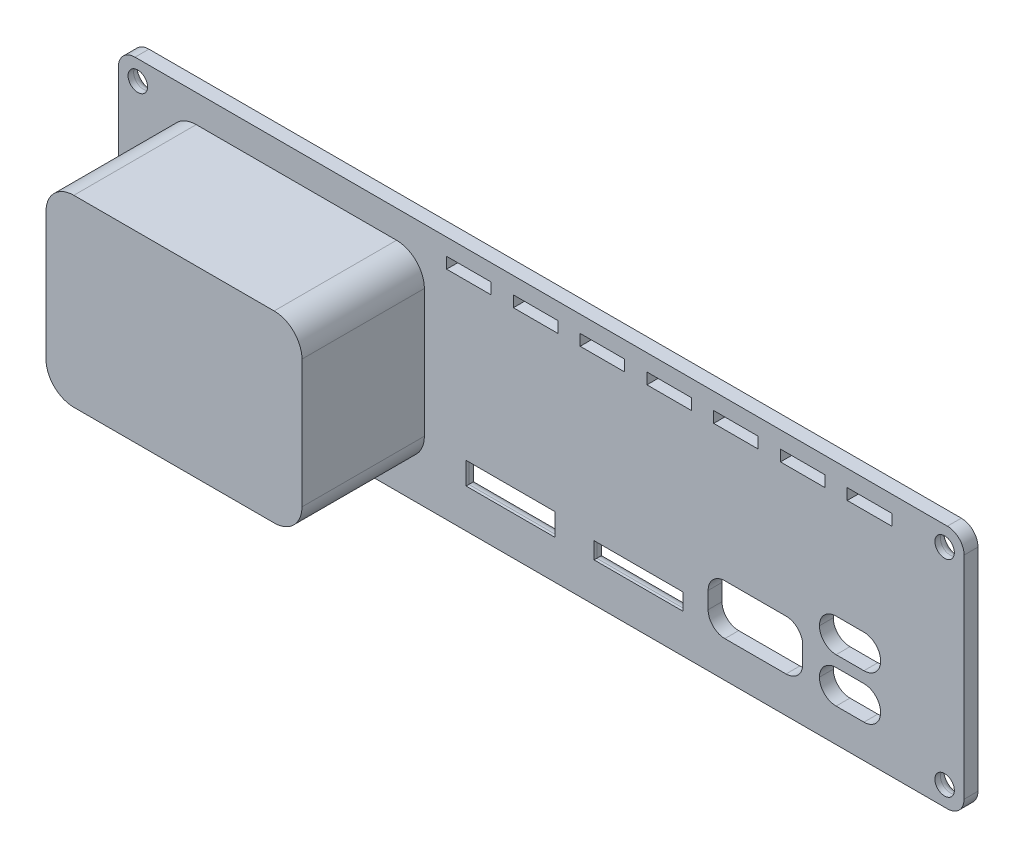
SolidWorks part; units mm, degrees
ref_plane "Front Plane" through (0, 0, 0) normal (0, 0, 1) x (1, 0, 0)
ref_plane "Top Plane" through (0, 0, 0) normal (0, 1, 0) x (1, 0, 0)
ref_plane "Right Plane" through (0, 0, 0) normal (1, 0, 0) x (0, 0, -1)
sketch "Sketch1" plane through (0, 0, 0) normal (0, 0, 1) x (1, 0, 0)
  line L1 (76, -22) -> (-76, -22)
  line L2 (76, -22) -> (76, 22)
  line L3 (76, 22) -> (-76, 22)
  line L4 (-76, -22) -> (-76, 22)
  line L5 (76, -22) -> (-76, 22) construction
  line L6 (76, 22) -> (-76, -22) construction
  point P0 (0, 0)
  dimension "D1" = 152
  dimension "D2" = 44
extrude "main_body" add sketch "Sketch1" along normal blind 2.5
fillet "body_corners" radius 3 4 edges at (-76, -22, 1.25) (76, -22, 1.25) (76, 22, 1.25) (-76, 22, 1.25)
sketch "Sketch2" plane through (0, 0, 2.5) normal (0, 0, 1) x (1, 0, 0)
  line L0 (-76, 18.5) -> (76, 18.5) construction
  line L1 (-76, 19) -> (-76, -19) construction
  line L2 (76, -19) -> (76, 19) construction
  line L3 (-72.5, 22) -> (-72.5, -22) construction
  line L4 (-76, -18.5) -> (76, -18.5) construction
  line L8 (73, 22) -> (-73, 22) construction
  line L9 (72.5, 22) -> (72.5, -22) construction
  line L10 (-73, -22) -> (73, -22) construction
  circle A1 centre (-72.5, -18.5) radius 1.75
  circle A2 centre (72.5, 18.5) radius 1.75
  circle A3 centre (72.5, -18.5) radius 1.75
  circle A4 centre (-72.5, 18.5) radius 1.75
  dimension "D5" = 3.5
  dimension "D6" = 3.5
  dimension "D7" = 3.5
  dimension "D8" = 3.5
  dimension "D1" = 3.5
  dimension "D2" = 3.5
  dimension "D3" = 3.5
  dimension "D4" = 3.5
extrude "mounting_holes" cut sketch "Sketch2" against normal through all
fillet "bolt_heads" radius 1.5 4 edges at (-70.75, -18.5, 0) (-70.75, 18.5, 0) (74.25, -18.5, 0) (74.25, 18.5, 0)
sketch "Sketch3" plane through (0, 0, 2.5) normal (0, 0, 1) x (1, 0, 0)
  line L0 (-76, 5) -> (76, 5) construction
  line L1 (-76, 19) -> (-76, -19) construction
  line L2 (76, -19) -> (76, 19) construction
  line L3 (73, 22) -> (-73, 22) construction
  line L4 (-73, -22) -> (73, -22) construction
  line L5 (0, 22) -> (0, -22) construction
  line L6 (76, -19) -> (76, 19) construction
  line L8 (50, -2) -> (61, -2)
  line L10 (50, -2) -> (50, -8)
  line L11 (50, -8) -> (61, -8)
  line L13 (61, -2) -> (61, -8)
  line L14 (50, -2) -> (61, -8) construction
  line L16 (50, -8) -> (61, -2) construction
  line L17 (30, -6.5) -> (47, -6.5)
  line L18 (30, -6.5) -> (30, -15.5)
  line L19 (30, -15.5) -> (47, -15.5)
  line L20 (47, -6.5) -> (47, -15.5)
  line L21 (30, -6.5) -> (47, -15.5) construction
  line L22 (30, -15.5) -> (47, -6.5) construction
  line L23 (50, -10) -> (61, -10)
  line L24 (50, -10) -> (50, -16)
  line L25 (50, -16) -> (61, -16)
  line L26 (61, -10) -> (61, -16)
  line L27 (50, -10) -> (61, -16) construction
  line L28 (50, -16) -> (61, -10) construction
  line L29 (9.5, -12) -> (25.5, -12)
  line L30 (9.5, -12) -> (9.5, -15)
  line L31 (9.5, -15) -> (25.5, -15)
  line L32 (25.5, -12) -> (25.5, -15)
  line L33 (9.5, -12) -> (25.5, -15) construction
  line L34 (9.5, -15) -> (25.5, -12) construction
  line L35 (-13.5, -11) -> (2.5, -11)
  line L36 (-13.5, -11) -> (-13.5, -15)
  line L37 (-13.5, -15) -> (2.5, -15)
  line L38 (2.5, -11) -> (2.5, -15)
  line L39 (-13.5, -11) -> (2.5, -15) construction
  line L40 (-13.5, -15) -> (2.5, -11) construction
  point P15 (-5.5, -13)
  point P34 (55.5, -13)
  point P36 (55.5, -5)
  point P41 (38.5, -11)
  point P49 (55.5, -16)
  point P51 (17.5, -13.5)
  dimension "D7" = 73.5
  dimension "D8" = 7
  dimension "D9" = 4
  dimension "D10" = 16
  dimension "D12" = 50.5
  dimension "D13" = 6
  dimension "D14" = 11
  dimension "D15" = 29
  dimension "D1" = 17
  dimension "D16" = 6
  dimension "D17" = 15
  dimension "D18" = 15
  dimension "D19" = 11
  dimension "D20" = 6
  dimension "D21" = 17
  dimension "D22" = 9
  dimension "D23" = 8
  dimension "D25" = 14
  dimension "D26" = 6.5
  dimension "D28" = 7
  dimension "D30" = 3
  dimension "D31" = 16
extrude "connectors" cut sketch "Sketch3" against normal through all
fillet "usb_host_corners" radius 3 4 edges at (47, -15.5, 1.25) (47, -6.5, 1.25) (30, -15.5, 1.25) (30, -6.5, 1.25)
fillet "usb_dfu_corners" radius 3 8 edges at (61, -2, 1.25) (61, -8, 1.25) (50, -8, 1.25) (50, -2, 1.25) (61, -10, 1.25) (61, -16, 1.25) (50, -16, 1.25) (50, -10, 1.25)
fillet "sd_rot_corners" radius 2 8 edges at (-5.5, -11, 0) (-13.5, -13, 0) (-5.5, -15, 0) (2.5, -13, 0) (9.5, -13.5, 0) (25.5, -13.5, 0) (17.5, -15, 0) (17.5, -12, 0)
sketch "Sketch4" plane through (0, 0, 2.5) normal (0, 0, 1) x (1, 0, 0)
  line L0 (-76, 19) -> (-76, -19) construction
  line L1 (-67, 17) -> (-21, 17)
  line L2 (-67, 17) -> (-67, -16)
  line L3 (-67, -16) -> (-21, -16)
  line L4 (-21, 17) -> (-21, -16)
  line L5 (-67, 17) -> (-21, -16) construction
  line L6 (-67, -16) -> (-21, 17) construction
  line L7 (-73, -22) -> (73, -22) construction
  point P0 (-44, 0.5)
  dimension "D1" = 9
  dimension "D2" = 6
  dimension "D3" = 33
  dimension "D4" = 46
extrude "keyer" add sketch "Sketch4" along normal blind 22
sketch "Sketch5" plane through (0, 0, 24.5) normal (0, 0, 1) x (1, 0, 0)
  line L0 (-67, -16) -> (-21, 17) construction
  line L1 (-21, 17) -> (-67, 17) construction
  line L2 (-22, -15) -> (-66, -15)
  line L3 (-67, 17) -> (-21, -16) construction
  line L4 (-22, -15) -> (-22, 16)
  line L5 (-22, 16) -> (-66, 16)
  line L6 (-66, -15) -> (-66, 16)
  line L7 (-22, -15) -> (-66, 16) construction
  line L8 (-22, 16) -> (-66, -15) construction
  line L9 (-21, -16) -> (-21, 17) construction
  point P4 (-44, 0.5)
  dimension "D1" = 1
  dimension "D2" = 1
extrude "keyer_cut" cut sketch "Sketch5" against normal through all from offset 1 offset against normal yes
sketch "Sketch6" plane through (0, 0, 0) normal (0, 0, -1) x (-1, 0, 0)
  line L1 (69, -20) -> (-69, -20)
  line L2 (69, -20) -> (69, 20)
  line L3 (69, 20) -> (-69, 20)
  line L4 (-69, -20) -> (-69, 20)
  line L5 (69, -20) -> (-69, 20) construction
  line L6 (69, 20) -> (-69, -20) construction
  point P0 (0, 0)
  dimension "D1" = 138
  dimension "D2" = 40
extrude "paint_slot" cut sketch "Sketch6" against normal blind 0.01
fillet "paint_slot_corners" radius 5 4 edges at (-69, -20, 0.005) (-69, 20, 0.005) (69, -20, 0.005) (69, 20, 0.005)
sketch "Sketch7" plane through (0, 0, 0.01) normal (0, 0, -1) x (-1, 0, 0)
  line L0 (-69, 18) -> (69, 18) construction
  line L1 (-69, 15) -> (-69, -15) construction
  line L2 (69, -15) -> (69, 15) construction
  line L3 (64, 20) -> (-64, 20) construction
  line L4 (-76, -19) -> (-76, 19) construction
  line L5 (-55, 17) -> (-63, 17)
  line L6 (-55, 17) -> (-55, 19)
  line L7 (-55, 19) -> (-63, 19)
  line L8 (-63, 17) -> (-63, 19)
  line L9 (-55, 17) -> (-63, 19) construction
  line L10 (-55, 19) -> (-63, 17) construction
  line L11 (-43, 17) -> (-51, 17)
  line L12 (-43, 17) -> (-43, 19)
  line L13 (-43, 19) -> (-51, 19)
  line L14 (-51, 17) -> (-51, 19)
  line L15 (-43, 17) -> (-51, 19) construction
  line L16 (-43, 19) -> (-51, 17) construction
  line L17 (-31, 17) -> (-39, 17)
  line L18 (-31, 17) -> (-31, 19)
  line L19 (-31, 19) -> (-39, 19)
  line L20 (-39, 17) -> (-39, 19)
  line L21 (-31, 17) -> (-39, 19) construction
  line L22 (-31, 19) -> (-39, 17) construction
  line L23 (-19, 17) -> (-27, 17)
  line L24 (-19, 17) -> (-19, 19)
  line L25 (-19, 19) -> (-27, 19)
  line L26 (-27, 17) -> (-27, 19)
  line L27 (-19, 17) -> (-27, 19) construction
  line L28 (-19, 19) -> (-27, 17) construction
  line L29 (-7, 17) -> (-15, 17)
  line L30 (-7, 17) -> (-7, 19)
  line L31 (-7, 19) -> (-15, 19)
  line L32 (-15, 17) -> (-15, 19)
  line L33 (-7, 17) -> (-15, 19) construction
  line L34 (-7, 19) -> (-15, 17) construction
  line L35 (5, 17) -> (-3, 17)
  line L36 (5, 17) -> (5, 19)
  line L37 (5, 19) -> (-3, 19)
  line L38 (-3, 17) -> (-3, 19)
  line L39 (5, 17) -> (-3, 19) construction
  line L40 (5, 19) -> (-3, 17) construction
  line L41 (17, 17) -> (9, 17)
  line L42 (17, 17) -> (17, 19)
  line L43 (17, 19) -> (9, 19)
  line L44 (9, 17) -> (9, 19)
  line L45 (17, 17) -> (9, 19) construction
  line L46 (17, 19) -> (9, 17) construction
  point P8 (-59, 18)
  point P13 (-47, 18)
  point P18 (-35, 18)
  point P23 (-23, 18)
  point P28 (-11, 18)
  point P33 (1, 18)
  point P38 (13, 18)
  dimension "D1" = 2
  dimension "D2" = 8
  dimension "D3" = 2
  dimension "D4" = 13
  dimension "D5" = 4
  dimension "D6" = 8
  dimension "D7" = 4
  dimension "D8" = 4
  dimension "D9" = 4
  dimension "D10" = 8
  dimension "D11" = 2
  dimension "D12" = 2
  dimension "D13" = 8
  dimension "D14" = 2
  dimension "D15" = 8
  dimension "D16" = 2
  dimension "D17" = 4
  dimension "D18" = 8
  dimension "D19" = 2
  dimension "D20" = 4
  dimension "D21" = 8
  dimension "D22" = 2
extrude "batt_fan_exhaust" cut sketch "Sketch7" against normal through all
fillet "Fillet1" radius 5 8 edges at (-21, -16, 13.5) (-66, -15, 11.755) (-67, 17, 13.5) (-21, 17, 13.5) (-66, 16, 11.755) (-67, -16, 13.5) (-22, 16, 11.755) (-22, -15, 11.755)
